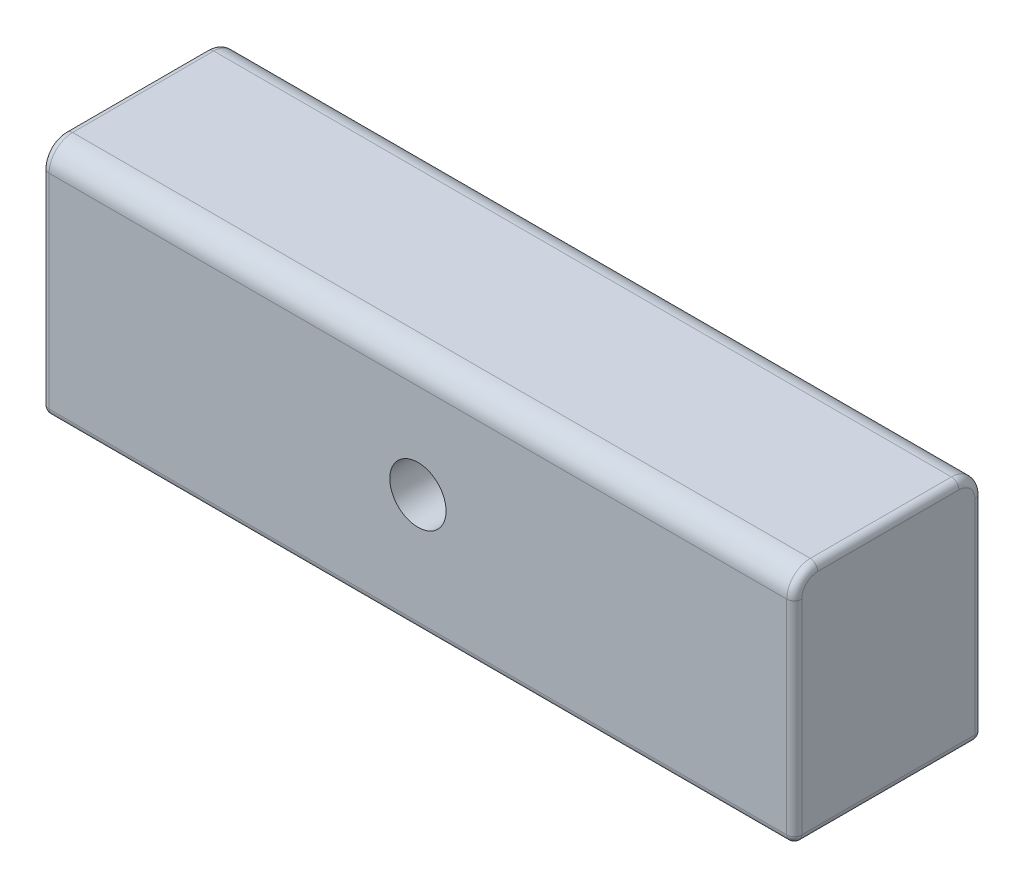
SolidWorks part; units mm, degrees
ref_plane "Front Plane" through (0, 0, 0) normal (0, 0, 1) x (1, 0, 0)
ref_plane "Top Plane" through (0, 0, 0) normal (0, 1, 0) x (1, 0, 0)
ref_plane "Right Plane" through (0, 0, 0) normal (1, 0, 0) x (0, 0, -1)
sketch "Sketch2" plane through (0, 0, 0) normal (0, 0, 1) x (1, 0, 0)
  line L1 (0, 0) -> (50.8, 0)
  line L2 (0, 0) -> (0, 15.875)
  line L3 (0, 15.875) -> (50.8, 15.875)
  line L4 (50.8, 0) -> (50.8, 15.875)
  dimension "D1" = 50.8
  dimension "D2" = 15.875
extrude "Extrude1" add sketch "Sketch2" along normal blind 12.7
hole_wizard "#10-24 Tapped Hole1" positions "3DSketch1" profile "Sketch3" tap size "#10-24" standard "Ansi Inch" end condition up to next
sketch3d "3DSketch1"
  line L0 (0, 7.9375, 12.7) -> (50.8, 7.9375, 12.7) construction
  line L1 (0, 15.875, 12.7) -> (0, 0, 12.7) construction
  line L2 (50.8, 0, 12.7) -> (50.8, 15.875, 12.7) construction
  point P0 (25.4, 7.9375, 12.7)
sketch "Sketch3" plane through (25.4, 7.9375, 12.7) normal (1, 0, 0) x (0, -1, 0)
  line L0 (0, 0) -> (0, 12.7)
  line L1 (0, 12.7) -> (1.8986, 12.7)
  line L2 (1.8986, 12.7) -> (1.8986, 0)
  line L5 (1.8986, 0) -> (0, 0)
  line L11 (0, -6.35) -> (0, 107.95) construction
  dimension "Thread Major Dia." = 3.7973
  dimension "Thru Tap Drill Depth" = 12.7
fillet "Fillet1" radius 1.5875 2 edges at (25.4, 15.875, 12.7) (25.4, 15.875, 0)
fillet "Fillet2" radius 0.508 15 edges at (50.8, 7.1437, 12.7) (50.8, 15.41, 12.235) (50.8, 15.875, 6.35) (50.8, 15.41, 0.465) (0, 7.1437, 12.7) (0, 15.41, 12.235) (0, 15.875, 6.35) (0, 15.41, 0.465) (0, 0, 6.35) (25.4, 0, 12.7) (50.8, 0, 6.35) (25.4, 0, 0) (50.8, 7.1437, 0) (0, 7.1437, 0) (23.5014, 7.9375, 0)
